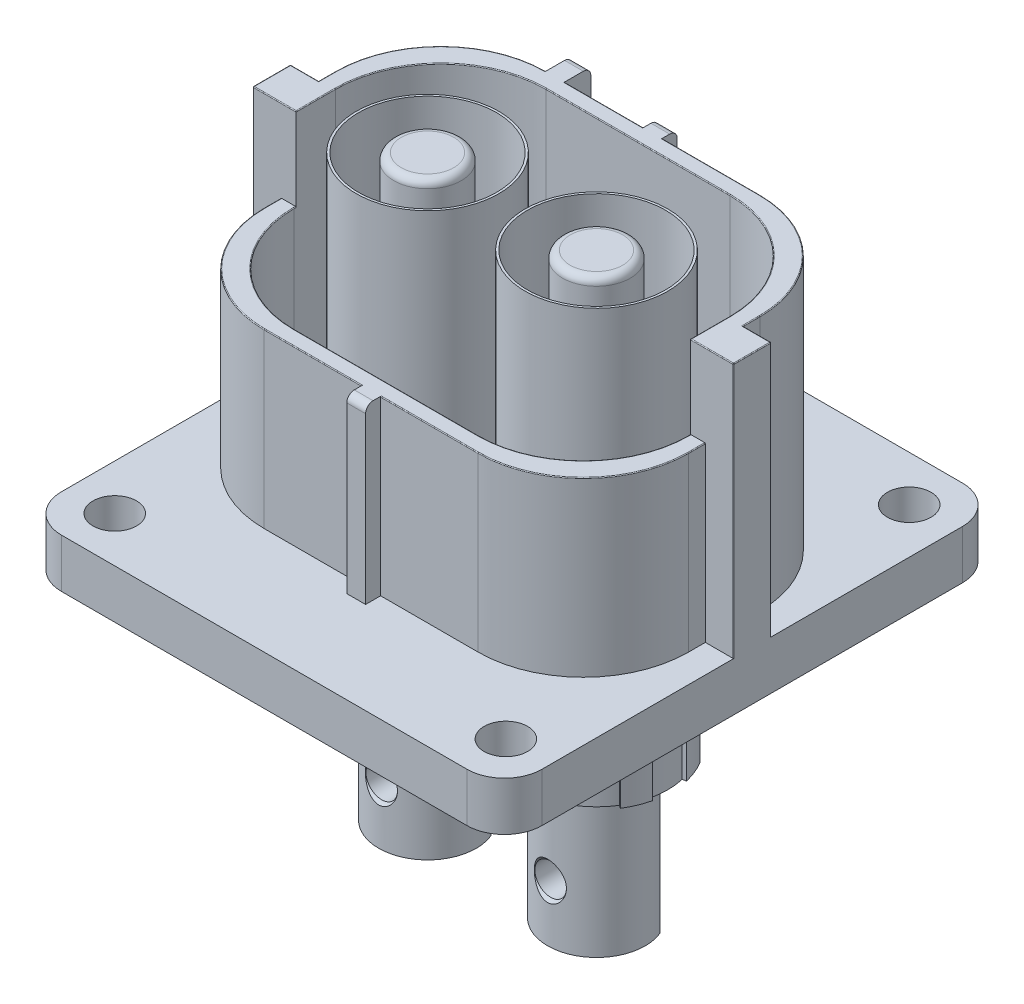
SolidWorks part; units mm, degrees
note: The reader was unsure of these and kept them because the rebuilt part matched: shared geometry of "Sketch1<5>", "Sketch1<6>", "Sketch1<7>", "Sketch1<8>", "Sketch1<9>".
ref_plane "Front Plane" through (0, 0, 0) normal (0, 0, 1) x (1, 0, 0)
ref_plane "Top Plane" through (0, 0, 0) normal (0, 1, 0) x (1, 0, 0)
ref_plane "Right Plane" through (0, 0, 0) normal (1, 0, 0) x (0, 0, -1)
sketch "Sketch1" plane through (0, 0, 0) normal (0, 1, 0) x (1, 0, 0)
  line L0 (-32, -2.5) -> (-28.25, -2.5)
  line L1 (-32, -28) -> (-32, 28)
  line L2 (-27, -33) -> (27, -33)
  line L3 (32, -28) -> (32, 28)
  line L4 (-27, 33) -> (27, 33)
  line L5 (-14.25, 18.75) -> (14.25, 18.75)
  line L6 (-28.25, 4.75) -> (-28.25, -4.75)
  line L7 (-14.25, -18.75) -> (14.25, -18.75)
  line L8 (28.25, 4.75) -> (28.25, -4.75)
  line L9 (-28.25, 18.75) -> (28.25, -18.75) construction
  line L10 (-28.25, -18.75) -> (28.25, 18.75) construction
  line L11 (28.25, -2.5) -> (32, -2.5)
  line L12 (-32, 2.5) -> (-28.25, 2.5)
  line L13 (28.25, 2.5) -> (32, 2.5)
  line L14 (-1.25, 19.75) -> (-11.75, 19.75) construction
  line L15 (-12.25, 16.75) -> (12.25, 16.75)
  line L16 (-26.25, 2.75) -> (-26.25, -2.75)
  line L17 (-12.25, -16.75) -> (12.25, -16.75)
  line L18 (26.25, 2.75) -> (26.25, -2.75)
  line L19 (-26.25, 16.75) -> (26.25, -16.75) construction
  line L20 (-26.25, -16.75) -> (26.25, 16.75) construction
  line L21 (-1.25, 20.75) -> (1.25, 20.75)
  line L22 (-1.25, 20.75) -> (-1.25, 18.75)
  line L23 (-26.25, 0) -> (26.25, 0) construction
  line L24 (1.25, 20.75) -> (1.25, 18.75)
  line L25 (-1.25, 20.75) -> (0, 18.75) construction
  line L26 (0, 18.75) -> (1.25, 20.75) construction
  line L27 (-1.25, -18.75) -> (-1.25, -20.75)
  line L28 (-1.25, -20.75) -> (1.25, -20.75)
  line L29 (1.25, -18.75) -> (1.25, -20.75)
  line L30 (0, -18.75) -> (1.25, -20.75) construction
  line L31 (-1.25, -20.75) -> (0, -18.75) construction
  line L32 (28.25, -2.5) -> (26.25, -2.5)
  line L33 (-14.25, 18.75) -> (-14.25, 22.25)
  line L34 (-14.25, 22.25) -> (-11.75, 22.25)
  line L35 (-11.75, 18.75) -> (-11.75, 22.25)
  line L36 (-12.9821, 18.75) -> (-11.75, 22.25) construction
  line L37 (-14.25, 22.25) -> (-12.9821, 18.75) construction
  line L38 (-4, 12.75) -> (4, 12.75)
  line L39 (-5, 11.75) -> (-5, 7.75)
  line L40 (-4, 6.75) -> (4, 6.75)
  line L41 (5, 11.75) -> (5, 7.75)
  line L42 (-5, 12.75) -> (5, 6.75) construction
  line L43 (-5, 6.75) -> (5, 12.75) construction
  line L44 (-3.5, 11.75) -> (3.5, 11.75)
  line L45 (-4, 11.25) -> (-4, 8.25)
  line L46 (-3.5, 7.75) -> (3.5, 7.75)
  line L47 (4, 11.25) -> (4, 8.25)
  line L48 (-4, 11.75) -> (4, 7.75) construction
  line L49 (-4, 7.75) -> (4, 11.75) construction
  line L50 (-28.25, -2.5) -> (-26.25, -2.5)
  line L51 (-4, 9.75) -> (4, 9.75) construction
  line L52 (-1.925, 9.75) -> (1.925, 9.75) construction
  arc A0 (27, -33) -> (32, -28) centre (27, -28) ccw
  arc A1 (32, 28) -> (27, 33) centre (27, 28) ccw
  arc A2 (-32, 28) -> (-27, 33) centre (-27, 28) cw
  arc A3 (-32, -28) -> (-27, -33) centre (-27, -28) ccw
  circle A4 centre (-25.95, -26.95) radius 2.9
  circle A5 centre (-25.95, 26.95) radius 2.9
  circle A6 centre (26.1, -26.9156) radius 2.9
  circle A7 centre (25.95, 26.95) radius 2.9
  arc A8 (14.25, -18.75) -> (28.25, -4.75) centre (14.25, -4.75) ccw
  arc A9 (-28.25, -4.75) -> (-14.25, -18.75) centre (-14.25, -4.75) ccw
  arc A10 (-14.25, 18.75) -> (-28.25, 4.75) centre (-14.25, 4.75) ccw
  arc A11 (14.25, 18.75) -> (28.25, 4.75) centre (14.25, 4.75) cw
  arc A12 (-26.25, -2.75) -> (-12.25, -16.75) centre (-12.25, -2.75) ccw
  arc A13 (12.25, -16.75) -> (26.25, -2.75) centre (12.25, -2.75) ccw
  arc A14 (12.25, 16.75) -> (26.25, 2.75) centre (12.25, 2.75) cw
  arc A15 (-12.25, 16.75) -> (-26.25, 2.75) centre (-12.25, 2.75) ccw
  circle A16 centre (-11.25, 0) radius 9.5
  circle A17 centre (11.25, 0) radius 9.5
  arc A18 (4, 12.75) -> (5, 11.75) centre (4, 11.75) cw
  arc A19 (4, 6.75) -> (5, 7.75) centre (4, 7.75) ccw
  arc A20 (-5, 7.75) -> (-4, 6.75) centre (-4, 7.75) ccw
  arc A21 (-4, 12.75) -> (-5, 11.75) centre (-4, 11.75) ccw
  arc A22 (4, 8.25) -> (3.5, 7.75) centre (3.5, 8.25) cw
  arc A23 (4, 11.25) -> (3.5, 11.75) centre (3.5, 11.25) ccw
  arc A24 (-4, 11.25) -> (-3.5, 11.75) centre (-3.5, 11.25) cw
  arc A25 (-4, 8.25) -> (-3.5, 7.75) centre (-3.5, 8.25) ccw
  circle A26 centre (-11.25, 0) radius 9.2
  circle A27 centre (11.25, 0) radius 9.2
  circle A28 centre (-11.25, 0) radius 4.5
  circle A29 centre (11.25, 0) radius 4.5
  circle A30 centre (-1.925, 9.75) radius 1.5
  circle A31 centre (1.925, 9.75) radius 1.5
  point P0 (0, 0)
  point P1 (0, 0)
  point P47 (0, 0)
  point P64 (0, 18.75)
  point P65 (0, -18.75)
  point P78 (-12.9821, 18.75)
  point P90 (0, 9.75)
  point P107 (0, 9.75)
  dimension "D3" = 5
  dimension "D5" = 5.8
  dimension "D6" = 5.8
  dimension "D4" = 5.8
  dimension "D7" = 5.8
  dimension "D18" = 14
  dimension "D21" = 14
  dimension "D31" = 15
  dimension "D32" = 15
  dimension "D33" = 12
  dimension "D36" = 1
  dimension "D40" = 0.5
  dimension "D41" = 0.3
  dimension "D42" = 19
  dimension "D43" = 19
  dimension "D44" = 0.3
  dimension "D45" = 1.925
  dimension "D1" = 66
  dimension "D2" = 64
  dimension "D8" = 6.05
  dimension "D9" = 6.05
  dimension "D10" = 6.05
  dimension "D11" = 6.05
  dimension "D12" = 6.05
  dimension "D13" = 6.05
  dimension "D14" = 37.5
  dimension "D15" = 56.5
  dimension "D16" = 30.5
  dimension "D17" = 5
  dimension "D19" = 2
  dimension "D20" = 2
  dimension "D22" = 2.5
  dimension "D23" = 2
  dimension "D24" = 2.5
  dimension "D25" = 2
  dimension "D26" = 1.25
  dimension "D27" = 10.5
  dimension "D28" = 2.5
  dimension "D29" = 0
  dimension "D30" = 3.5
  dimension "D34" = 10
  dimension "D35" = 0
  dimension "D37" = 1
  dimension "D38" = 1
  dimension "D39" = 6
  dimension "D46" = 1.925
extrude "Boss-Extrude1" add sketch "Sketch1" along normal blind 6.5 contours L5 A11 L8 L13 L3 A1 L4 A2 L1 L12 L6 A10 L33 L34 L35 L22 L21 L24 A7 A5 | L12 L1 L0 L6 | A9 L6 L0 L1 A3 L2 A0 L3 L11 L8 A8 L7 L29 L28 L27 A6 A4 | L15 A15 L16 A12 L17 A13 L18 A14 A21 L38 A18 L41 A19 L40 A20 L39 A17 A16 | L24 L21 L22 L5 | L5 L35 L34 L33 | L29 L7 L27 L28 | A11 L5 A10 L6 A9 L7 A8 L8 A15 L15 A14 L18 A13 L17 A12 L16 | A16 A26 | A17 A27 | L13 L8 L11 L3 | A27 | A26 | A13 L17 A12 L16 L50 L6 A9 L7 A8 L8 L32 L18 | A29 | A28 | L38 A21 L39 A20 L40 A19 L41 A18 A25 L45 A24 L44 A23 L47 A22 L46 | L45 A25 L46 A22 L47 A23 L44 A24 A31 A30
extrude "Boss-Extrude2" add sketch "Sketch1<5>" along normal blind 29.5 contours A13 L17 A12 L16 L50 L6 A9 L7 A8 L8 L32 L18 | L29 L7 L27 L28
sketch "Sketch1<5>" plane through (0, 0, 0) normal (0, 1, 0) x (1, 0, 0) same geometry as "Sketch1"
extrude "Boss-Extrude3" add sketch "Sketch1<6>" along normal blind 42 contours A16 A26 | A17 A27
sketch "Sketch1<6>" plane through (0, 0, 0) normal (0, 1, 0) x (1, 0, 0) same geometry as "Sketch1"
extrude "Boss-Extrude4" add sketch "Sketch1<7>" along normal blind 42 contours A28 | A29
sketch "Sketch1<7>" plane through (0, 0, 0) normal (0, 1, 0) x (1, 0, 0) same geometry as "Sketch1"
extrude "Boss-Extrude5" add sketch "Sketch1<8>" along normal blind 40.5 contours L12 L1 L0 L6 | A15 L15 A14 L18 L32 L8 A11 L5 A10 L6 L50 L16 | L5 L35 L34 L33 | L24 L21 L22 L5 | L13 L8 L11 L3
sketch "Sketch1<8>" plane through (0, 0, 0) normal (0, 1, 0) x (1, 0, 0) same geometry as "Sketch1"
fillet "Fillet1" radius 1 3 edges at (0, 29.5, 20.75) (-13, 40.5, -22.25) (0, 40.5, -20.75)
fillet "Fillet2" radius 1 2 edges at (11.25, 42, 4.5) (-11.25, 42, 4.5)
fillet "Fillet3" radius 0.1 32 edges at (28.25, 29.5, 3.625) (24.1495, 29.5, 14.6495) (-28.25, 29.5, 3.625) (-7.75, 29.5, 18.75) (-26.25, 29.5, 2.625) (26.25, 29.5, 2.625) (22.1495, 29.5, 12.6495) (0, 29.5, 16.75) (-26.25, 40.5, -0.125) (-22.1495, 40.5, -12.6495) (0, 40.5, -16.75) (22.1495, 40.5, -12.6495) (-28.25, 40.5, -3.625) (7.75, 40.5, -18.75) (28.25, 40.5, -3.625) (7.75, 29.5, 18.75) (-24.1495, 29.5, 14.6495) (-22.1495, 29.5, 12.6495) (-32, 23.5, 2.5) (-32, 23.5, -2.5) (-32, 40.5, 0) (-29.125, 40.5, 2.5) (-30.125, 40.5, -2.5) (26.25, 40.5, -0.125) (32, 23.5, -2.5) (32, 23.5, 2.5) (29.125, 40.5, 2.5) (32, 40.5, 0) (30.125, 40.5, -2.5) (-24.1495, 40.5, -14.6495) (-6.5, 40.5, -18.75) (24.1495, 40.5, -14.6495)
extrude "Boss-Extrude6" add sketch "Sketch1<9>" along normal blind 18.5 contours L38 A21 L39 A20 L40 A19 L41 A18 A25 L45 A24 L44 A23 L47 A22 L46
sketch "Sketch1<9>" plane through (0, 0, 0) normal (0, 1, 0) x (1, 0, 0) same geometry as "Sketch1"
sketch "Sketch2" plane through (0, 0, 0) normal (0, -1, 0) x (1, 0, 0)
  line L0 (-1.925, -9.75) -> (1.925, -9.75) construction
  line L1 (-11.25, 0) -> (-7.4232, 9.2388)
  line L2 (-3.5, -6.75) -> (3.5, -6.75)
  line L3 (-4.5, -7.75) -> (-4.5, -11.75)
  line L4 (-3.5, -12.75) -> (3.5, -12.75)
  line L5 (4.5, -7.75) -> (4.5, -11.75)
  line L6 (-4.5, -6.75) -> (4.5, -12.75) construction
  line L7 (-4.5, -12.75) -> (4.5, -6.75) construction
  line L8 (-11.25, 0) -> (-16.5418, 8.4851)
  line L9 (-15.0768, 9.2388) -> (-11.25, 0)
  line L10 (-13.508, 9.7417) -> (-11.25, 0)
  line L11 (-11.25, 0) -> (-8.992, 9.7417)
  line L12 (-11.25, 0) -> (-20.9917, 2.258)
  line L13 (-5.9582, 8.4851) -> (-11.25, 0)
  line L14 (-11.25, 10) -> (-11.25, 0)
  line L15 (-19.7351, 5.2918) -> (-11.25, 0)
  line L16 (-11.25, 0) -> (-19.7351, -5.2918)
  line L17 (-20.9917, -2.258) -> (-11.25, 0)
  line L18 (-11.25, 0) -> (-13.508, -9.7417)
  line L19 (-16.5418, -8.4851) -> (-11.25, 0)
  line L20 (-11.25, 0) -> (-5.9582, -8.4851)
  line L21 (-8.992, -9.7417) -> (-11.25, 0)
  line L22 (-11.25, 0) -> (-1.5083, -2.258)
  line L23 (-2.7649, -5.2918) -> (-11.25, 0)
  line L24 (-11.25, 0) -> (-2.7649, 5.2918)
  line L25 (-1.5083, 2.258) -> (-11.25, 0)
  line L26 (11.25, 0) -> (15.0768, 9.2388)
  line L27 (11.25, 0) -> (5.9582, 8.4851)
  line L28 (7.4232, 9.2388) -> (11.25, 0)
  line L29 (8.992, 9.7417) -> (11.25, 0)
  line L30 (11.25, 0) -> (13.508, 9.7417)
  line L31 (11.25, 0) -> (1.5083, 2.258)
  line L32 (16.5418, 8.4851) -> (11.25, 0)
  line L33 (11.25, 10) -> (11.25, 0)
  line L34 (2.7649, 5.2918) -> (11.25, 0)
  line L35 (11.25, 0) -> (2.7649, -5.2918)
  line L36 (1.5083, -2.258) -> (11.25, 0)
  line L37 (11.25, 0) -> (8.992, -9.7417)
  line L38 (5.9582, -8.4851) -> (11.25, 0)
  line L39 (11.25, 0) -> (16.5418, -8.4851)
  line L40 (13.508, -9.7417) -> (11.25, 0)
  line L41 (11.25, 0) -> (20.9917, -2.258)
  line L42 (19.7351, -5.2918) -> (11.25, 0)
  line L43 (11.25, 0) -> (19.7351, 5.2918)
  line L44 (20.9917, 2.258) -> (11.25, 0)
  circle A0 centre (1.925, -9.75) radius 1.5
  circle A1 centre (-1.925, -9.75) radius 1.5
  arc A2 (3.5, -12.75) -> (4.5, -11.75) centre (3.5, -11.75) ccw
  arc A3 (-4.5, -11.75) -> (-3.5, -12.75) centre (-3.5, -11.75) ccw
  arc A4 (3.5, -6.75) -> (4.5, -7.75) centre (3.5, -7.75) cw
  arc A5 (-3.5, -6.75) -> (-4.5, -7.75) centre (-3.5, -7.75) ccw
  circle A6 centre (-11.25, 0) radius 9.5
  circle A7 centre (11.25, 0) radius 9.5
  circle A8 centre (-11.25, 0) radius 10
  circle A9 centre (11.25, 0) radius 10
  point P4 (0, -9.75)
  point P23 (-11.25, 0)
  point P24 (11.25, 0)
  point P29 (11.25, 0)
  point P54 (-11.25, 0)
  point P73 (11.25, 0)
  circle M34 centre (-1.925, -9.75) radius 1.5
  circle M35 centre (1.925, -9.75) radius 1.5
  dimension "D3" = 1
  dimension "D4" = 45
  dimension "D6" = 0.5
  dimension "D1" = 9
  dimension "D2" = 6
  dimension "D5" = 8
  dimension "D7" = 18.9
  dimension "D8" = 9.45
  dimension "D10" = 18.9
  dimension "D11" = 9.45
extrude "Boss-Extrude7" add sketch "Sketch2" along normal blind 15.5 contours L9 A8 L8 A6 | L10 A8 L9 A6 | L10 A6 L9 | L9 A6 L8 | L15 A6 L12 | L15 A8 L12 A6 | L8 A6 L15 | L12 A6 L17 | L14 A6 L10 | L11 A6 L14 | L1 A6 L11 | L13 A8 L1 A6 | L1 A8 L11 A6 | L25 A8 L24 A6 | L23 A8 L22 A6 | L21 A8 L20 A6 | L19 A8 L18 A6 | L17 A8 L16 A6 | A9 A4 L2 A5 A8 L3 A3 L4 A2 L5 M35 M34 | L34 A9 L31 A7 | L28 A9 L27 A7 | L29 A9 L28 A7 | L26 A9 L30 A7 | L32 A9 L26 A7 | L44 A9 L43 A7 | L42 A9 L41 A7 | L40 A9 L39 A7 | L38 A9 L37 A7 | L36 A9 L35 A7
sketch "Sketch3" plane through (0, -15.5, 0) normal (0, -1, 0) x (1, 0, 0)
  line L0 (-25.95, 26.95) -> (26.1, 26.9156) construction
  line L1 (0.075, 26.9328) -> (0.075, 2.4328) construction
  line L2 (-17.2776, 2.4328) -> (17.2776, 2.4328) construction
  line L3 (-11.25, 0) -> (11.25, 0) construction
  line L4 (-17.2776, -2.4328) -> (17.2776, -2.4328) construction
  line L5 (-17.2776, -2.4328) -> (-5.2224, -2.4328)
  line L6 (5.2224, -2.4328) -> (17.2776, -2.4328)
  arc A0 (-5.2224, -2.4328) -> (-17.2776, -2.4328) centre (-11.25, 0) ccw
  arc A1 (17.2776, -2.4328) -> (5.2224, -2.4328) centre (11.25, 0) ccw
  dimension "D1" = 24.5
extrude "Boss-Extrude8" add sketch "Sketch3" along normal blind 19.5
sketch "Sketch5" plane through (0, 0, -2.4328) normal (0, 0, -1) x (-1, 0, 0)
  line L0 (0, 0) -> (0, -27.5) construction
  line L1 (-11.25, -27.5) -> (11.25, -27.5) construction
  point P8 (-11.25, -27.5)
  point P9 (11.25, -27.5)
  dimension "D1" = 27.5
hole_wizard "CSK for M5 Flat Head Machine Screw1" positions "Sketch6" profile "Sketch8" countersink size "M5" standard "ANSI Metric" end condition through all
sketch "Sketch6" plane through (0, 0, -2.4328) normal (0, 0, -1) x (-1, 0, 0)
  point P0 (-11.25, -27.5)
  point P3 (11.25, -27.5)
sketch "Sketch8" plane through (11.25, -27.5, -2.4328) normal (1, 0, 0) x (0, 1, 0)
  line L0 (0, 0) -> (0, 8.9328)
  line L1 (0, 8.9328) -> (2.5, 8.9328)
  line L2 (2.1, 8.5328) -> (2.1, 0.4)
  line L3 (2.1, 0.4) -> (2.5, 0)
  line L5 (2.5, 0) -> (0, 0)
  line L6 (-2.1, 0.4) -> (-2.5, 0) construction
  line L7 (2.5, 8.9328) -> (2.1, 8.5328)
  line L8 (-2.5, 8.9328) -> (-2.1, 8.5328) construction
  line L11 (0, -6.35) -> (0, 107.95) construction
  dimension "Thru Hole Dia." = 4.2
  dimension "Thru Hole Depth" = 8.9328
  dimension "Near C'Sink Dia." = 5
  dimension "Near C'Sink Angle" = 90
  dimension "Far C'Sink Dia." = 5
  dimension "Far C'Sink Angle" = 90
thread "Thread2" [suppressed] pitch 0.8 start angle 0, offset 0, length 8.5, pitch 0.8, diameter 4.2
ref_plane "Plane2" through (-9.15, -27.5, -2.0328) normal (0, -1, 0) x (1, 0, 0)
sketch "Thread Profile2" plane through (-9.15, -27.5, -2.0328) normal (0, -1, 0) x (1, 0, 0)
  line L0 (0, 0) -> (0, 0.8) construction
  line L1 (0, 0) -> (0.433, 0.25)
  line L2 (0.433, 0.25) -> (0.433, 0.35)
  line L3 (0.433, 0.35) -> (0, 0.6)
  line L4 (0.433, 0.3) -> (0, 0.3) construction
  line L11 (0, 0) -> (0, 0.6)
  point P2 (0, 0)
  dimension "Pitch" = 0.8
  dimension "Profile_Angle" = 60
  dimension "Profile_Land" = 0.1
  dimension "Profile_Height" = 0.433
thread "Thread3" [suppressed] pitch 0.8 start angle 0, offset 0, length 8.5, pitch 0.8, diameter 4.2
ref_plane "Plane3" through (13.35, -27.5, -2.0328) normal (0, -1, 0) x (1, 0, 0)
sketch "Thread Profile3" plane through (13.35, -27.5, -2.0328) normal (0, -1, 0) x (1, 0, 0)
  line L0 (0, 0) -> (0, 0.8) construction
  line L1 (0, 0) -> (0.433, 0.25)
  line L2 (0.433, 0.25) -> (0.433, 0.35)
  line L3 (0.433, 0.35) -> (0, 0.6)
  line L4 (0.433, 0.3) -> (0, 0.3) construction
  line L11 (0, 0) -> (0, 0.6)
  point P2 (0, 0)
  dimension "Pitch" = 0.8
  dimension "Profile_Angle" = 60
  dimension "Profile_Land" = 0.1
  dimension "Profile_Height" = 0.433
sketch "Sketch18" plane through (0, -15.5, 0) normal (0, -1, 0) x (1, 0, 0)
  circle A0 centre (-11.25, 0) radius 8
  circle A1 centre (11.25, 0) radius 8
  dimension "D1" = 16
  dimension "D2" = 16
split line "Split Line1"
